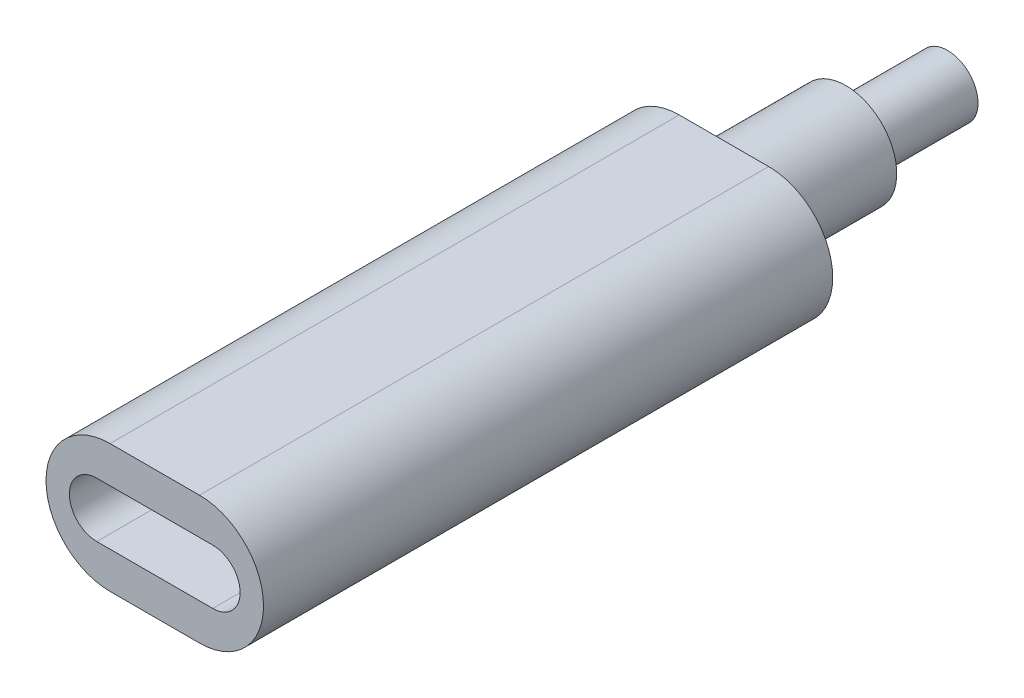
SolidWorks part; units mm, degrees
ref_plane "Front Plane" through (0, 0, 0) normal (0, 0, 1) x (1, 0, 0)
ref_plane "Top Plane" through (0, 0, 0) normal (0, 1, 0) x (1, 0, 0)
ref_plane "Right Plane" through (0, 0, 0) normal (1, 0, 0) x (0, 0, -1)
sketch "Sketch1" plane through (0, 0, 0) normal (0, 0, 1) x (1, 0, 0)
  line L0 (2.85, 0) -> (-2.85, 0) construction
  line L1 (2.85, -1.35) -> (-2.85, -1.35)
  line L2 (2.85, 1.35) -> (-2.85, 1.35)
  line L3 (2.2, 0) -> (-2.2, 0) construction
  line L4 (2.2, -3.15) -> (-2.2, -3.15)
  line L5 (2.2, 3.15) -> (-2.2, 3.15)
  arc A0 (2.85, -1.35) -> (2.85, 1.35) centre (2.85, 0) ccw
  arc A1 (-2.85, 1.35) -> (-2.85, -1.35) centre (-2.85, 0) ccw
  arc A2 (2.2, -3.15) -> (2.2, 3.15) centre (2.2, 0) ccw
  arc A3 (-2.2, 3.15) -> (-2.2, -3.15) centre (-2.2, 0) ccw
  point P2 (0, 0)
  point P8 (-4.2, 0)
  point P9 (4.2, 0)
  point P12 (0, 0)
  point P17 (-5.35, 0)
  point P18 (5.35, 0)
  dimension "D1" = 8.4
  dimension "D2" = 2.7
  dimension "D3" = 6.3
  dimension "D4" = 10.7
extrude "Boss-Extrude1" add sketch "Sketch1" against normal blind 28 contours L4 A3 L5 A2
extrude "Cut-Extrude1" cut sketch "Sketch1<3>" against normal blind 5 contours L1 A1 L2 A0
sketch "Sketch1<3>" plane through (0, 0, 0) normal (0, 0, 1) x (1, 0, 0) same geometry as "Sketch1"
sketch "Sketch3" plane through (0, 0, -28) normal (0, 0, -1) x (-1, 0, 0)
  circle A0 centre (0, 0) radius 2.5
  dimension "D1" = 5
extrude "Boss-Extrude2" add sketch "Sketch3" along normal blind 6
sketch "Sketch4" plane through (0, 0, -34) normal (0, 0, -1) x (-1, 0, 0)
  circle A0 centre (0, 0) radius 1.5
  dimension "D1" = 3
extrude "Boss-Extrude3" add sketch "Sketch4" along normal blind 5
